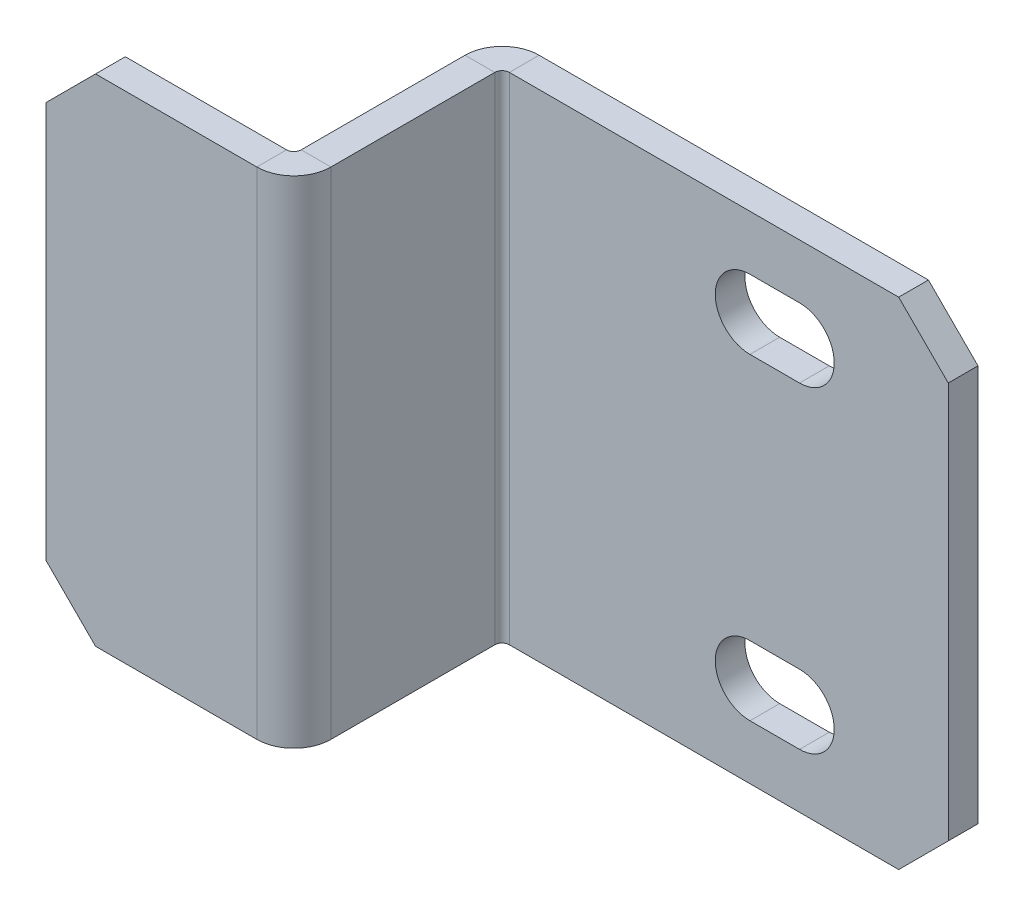
SolidWorks part; units mm, degrees
note: The reader was unsure of these and kept them because the rebuilt part matched: flange length of "边线-法兰1", "边线-法兰2".
material "Q235-A"
ref_plane "前视基准面" through (0, 0, 0) normal (0, 0, 1) x (1, 0, 0)
ref_plane "上视基准面" through (0, 0, 0) normal (0, 1, 0) x (1, 0, 0)
ref_plane "右视基准面" through (0, 0, 0) normal (1, 0, 0) x (0, 0, -1)
sketch "草图1" plane through (0, 0, 0) normal (0, 0, 1) x (1, 0, 0)
  line L1 (24, -25) -> (-24, -25)
  line L2 (24, -25) -> (24, 25)
  line L3 (24, 25) -> (-24, 25)
  line L4 (-24, -25) -> (-24, 25)
  line L5 (24, -25) -> (-24, 25) construction
  line L6 (24, 25) -> (-24, -25) construction
  point P0 (0, 0)
  dimension "D1" = 50
  dimension "D2" = 48
base flange "基体-法兰1" sketch "草图1" thickness 3 reverse thickness direction no parameters "D1"=0.7366
edge flange "边线-法兰1" sketch "草图8" flange angle 90 flange length 24 flange position material inside bend radius 0.7366 thickness 3 relief rectangular parameters "D6"=10
sketch "草图8" plane through (-24, 0, 0) normal (-1, 0, 0) x (0, -1, 0)
  line L0 (-25, 0) -> (25, 0) construction
  line L1 (-25, 0) -> (25, 0)
  line L2 (-25, 0) -> (-25, 21)
  line L3 (-25, 21) -> (25, 21)
  line L4 (25, 21) -> (25, 0)
bend "边线折弯1" bend radius 0.7366 bend angle 90 parameters "D5"=1
edge flange "边线-法兰2" sketch "草图11" flange angle 90 flange length 25 flange position material inside bend radius 0.7366 thickness 3 relief rectangular parameters "D6"=10
sketch "草图11" plane through (-24, 0, 21) normal (0, 0, -1) x (0, -1, 0)
  line L2 (-25, 0) -> (-25, 22)
  line L3 (-25, 22) -> (25, 22)
  line L4 (25, 22) -> (25, 0)
  line L5 (25, 0) -> (-25, 0) construction
  line L6 (25, 0) -> (-25, 0)
bend "边线折弯2" bend radius 0.7366 bend angle 90 parameters "D5"=2
chamfer "倒角1" distance 5 angle 45 4 edges at (24, -25, -1.5) (24, 25, -1.5) (-46, -25, 19.5) (-46, 25, 19.5)
hole_wizard "Ø7.0 (7) 直径孔1" positions "草图12" profile "草图13" hole size "Ø7.0" standard "GB" end condition through all
sketch "草图12" plane through (0, 0, -3) normal (0, 0, -1) x (-1, 0, 0)
  line L0 (-24, -20) -> (-24, 20) construction
  point P0 (-6.5, 16)
  point P2 (-6.5, -16)
  dimension "D1" = 32
  dimension "D2" = 16
  dimension "D3" = 17.5
sketch "草图13" plane through (6.5, 16, -3) normal (1, 0, 0) x (0, 1, 0)
  line L0 (0, 0) -> (0, 24)
  line L1 (0, 24) -> (3.5, 24)
  line L2 (3.5, 24) -> (3.5, 0)
  line L5 (3.5, 0) -> (0, 0)
  line L11 (0, -6.35) -> (0, 107.95) construction
  dimension "通孔孔直径" = 7
  dimension "通孔孔深度" = 24
sketch "草图14" plane through (0, 0, -3) normal (0, 0, -1) x (-1, 0, 0)
  line L0 (-9, 16) -> (-4, 16) construction
  line L1 (-9, 19.5) -> (-4, 19.5)
  line L2 (-9, 12.5) -> (-4, 12.5)
  line L3 (-9, -16) -> (-4, -16) construction
  line L4 (-9, -12.5) -> (-4, -12.5)
  line L5 (-9, -19.5) -> (-4, -19.5)
  arc A0 (-9, 19.5) -> (-9, 12.5) centre (-9, 16) ccw
  arc A1 (-4, 12.5) -> (-4, 19.5) centre (-4, 16) ccw
  arc A2 (-9, -12.5) -> (-9, -19.5) centre (-9, -16) ccw
  arc A3 (-4, -19.5) -> (-4, -12.5) centre (-4, -16) ccw
  point P2 (-6.5, 16)
  point P10 (-6.5, -16)
  dimension "D1" = 7
  dimension "D2" = 5
  dimension "D3" = 7
  dimension "D4" = 5
extrude "切除-拉伸1" cut sketch "草图14" against normal blind 10 normal cut yes
sketch "折弯-线1" [suppressed] plane through (0, 0, 0) normal (0, 1, 0) x (1, 0, 0)
sketch "边界框1" [suppressed] plane through (0, 0, 0) normal (0, 1, 0) x (1, 0, 0)
sheet metal parameters "钣金1" thickness 3 parameters "D1"=0.7366
flat pattern "平板型式1" [suppressed]
sketch "折弯-线2" plane through (0, 0, 0) normal (0, 1, 0) x (1, 0, 0)
sketch3d "边界框2" [suppressed]
  line L0 (25, -20, 0) -> (-25, -20, 0) construction
  line L1 (25, 20, 0) -> (-25, 20, 0) construction
  line L2 (25, -20, 0) -> (25, 20, 0) construction
  line L3 (-25, -20, 0) -> (-25, 20, 0) construction
sheet metal parameters "钣金2" thickness 3 parameters "D1"=0.7366
flat pattern "平板型式1"
sketch "折弯-线2" plane through (0, 0, 0) normal (0, 0, 1) x (1, 0, 0)
  line L0 (-23.02, 20) -> (-23.02, -20) construction
  line L1 (-23.02, 20) -> (-23.02, -20) construction
sketch3d "边界框2" [suppressed]
  line L0 (-51.04, -20, 0) -> (25, -20, 0) construction
  line L1 (-51.04, 20, 0) -> (25, 20, 0) construction
  line L2 (-51.04, -20, 0) -> (-51.04, 20, 0) construction
  line L3 (25, -20, 0) -> (25, 20, 0) construction
bend of the flat pattern "展平-<边线折弯1>1"
sheet metal parameters "钣金3" thickness 3 parameters "D1"=0.7366
flat pattern "平板型式1"
sketch "折弯-线2" plane through (0, 0, 0) normal (0, 0, 1) x (1, 0, 0)
  line L0 (-22.02, 25) -> (-22.02, -25) construction
  line L1 (-22.02, 25) -> (-22.02, -25) construction
  line L2 (-42.0601, 25) -> (-42.0601, -25) construction
  line L3 (-42.0601, 25) -> (-42.0601, -25) construction
sketch3d "边界框2" [suppressed]
  line L0 (-65.0801, -25, 0) -> (24, -25, 0) construction
  line L1 (-65.0801, 25, 0) -> (24, 25, 0) construction
  line L2 (-65.0801, -25, 0) -> (-65.0801, 25, 0) construction
  line L3 (24, -25, 0) -> (24, 25, 0) construction
bend of the flat pattern "展平-<边线折弯1>1"
bend of the flat pattern "展平-<边线折弯2>1"
sheet metal parameters "钣金4" thickness 3 parameters "D1"=0.7366
flat pattern "平板型式1"
sketch "折弯-线2" plane through (0, 0, 0) normal (0, 0, 1) x (1, 0, 0)
  line L0 (-22.02, 25) -> (-22.02, -25) construction
  line L1 (-22.02, 25) -> (-22.02, -25) construction
  line L2 (-42.0601, 25) -> (-42.0601, -25) construction
  line L3 (-42.0601, 25) -> (-42.0601, -25) construction
sketch3d "边界框2" [suppressed]
  line L0 (-65.0801, -25, 0) -> (24, -25, 0) construction
  line L1 (-65.0801, 25, 0) -> (24, 25, 0) construction
  line L2 (-65.0801, -25, 0) -> (-65.0801, 25, 0) construction
  line L3 (24, -25, 0) -> (24, 25, 0) construction
bend of the flat pattern "展平-<边线折弯1>1"
bend of the flat pattern "展平-<边线折弯2>1"
sheet metal parameters "钣金5" thickness 3 parameters "D1"=0.7366
flat pattern "平板型式1"
sketch "折弯-线2" plane through (0, 0, 0) normal (0, 0, 1) x (1, 0, 0)
  line L0 (-22.02, 25) -> (-22.02, -25) construction
  line L1 (-22.02, 25) -> (-22.02, -25) construction
  line L2 (-42.0601, 25) -> (-42.0601, -25) construction
  line L3 (-42.0601, 25) -> (-42.0601, -25) construction
sketch3d "边界框2" [suppressed]
  line L0 (-65.0801, -25, 0) -> (24, -25, 0) construction
  line L1 (-65.0801, 25, 0) -> (24, 25, 0) construction
  line L2 (-65.0801, -25, 0) -> (-65.0801, 25, 0) construction
  line L3 (24, -25, 0) -> (24, 25, 0) construction
bend of the flat pattern "展平-<边线折弯1>1"
bend of the flat pattern "展平-<边线折弯2>1"
